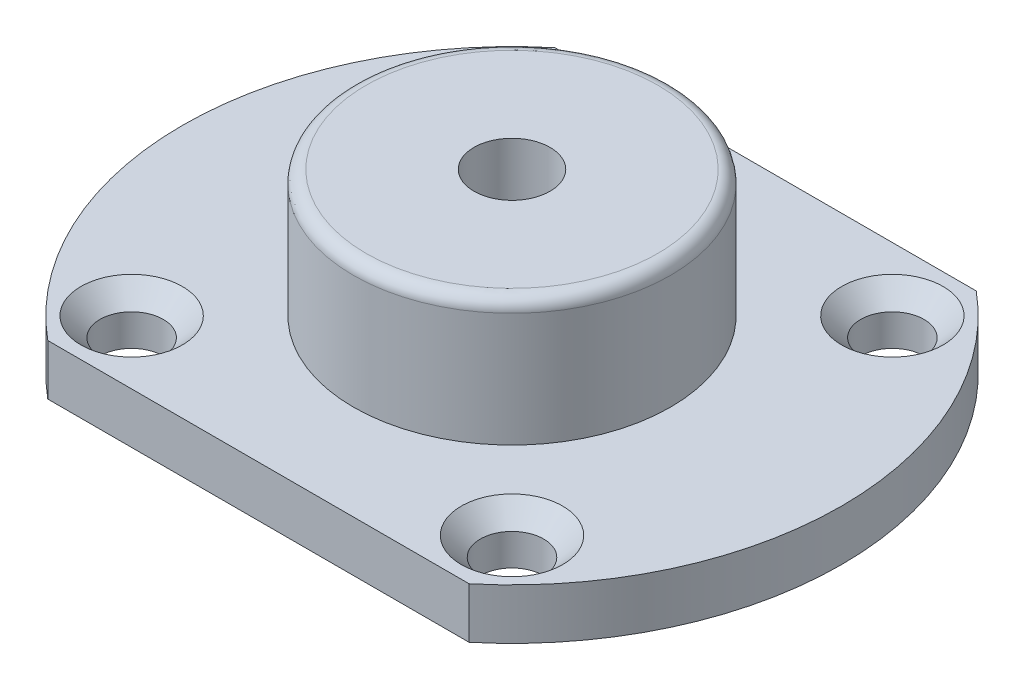
SolidWorks part; units mm, degrees
ref_plane "Спереди" through (0, 0, 0) normal (0, 0, 1) x (1, 0, 0)
ref_plane "Сверху" through (0, 0, 0) normal (0, 1, 0) x (1, 0, 0)
ref_plane "Справа" through (0, 0, 0) normal (1, 0, 0) x (0, 0, -1)
sketch "Эскиз1" plane through (0, 0, 0) normal (0, 1, 0) x (1, 0, 0)
  circle A0 centre (0, 0) radius 26
  dimension "D1" = 52
extrude "Бобышка-Вытянуть1" add sketch "Эскиз1" along normal blind 4
sketch "Эскиз2" plane through (0, 4, 0) normal (0, 1, 0) x (1, 0, 0)
  line L1 (-32.8601, -20) -> (32.8601, -20)
  line L2 (-32.8601, -20) -> (-32.8601, 20)
  line L3 (-32.8601, 20) -> (32.8601, 20)
  line L4 (32.8601, -20) -> (32.8601, 20)
  line L5 (0, 20) -> (0, -20) construction
  line L6 (-32.8601, 0) -> (32.8601, 0) construction
  point P0 (0, 0)
  dimension "D1" = 40
extrude "Вырез-Вытянуть1" cut sketch "Эскиз2" against normal blind 4 flip side to cut
sketch "Эскиз3" plane through (0, 4, 0) normal (0, 1, 0) x (1, 0, 0)
  circle A0 centre (0, 0) radius 12.5
  dimension "D1" = 25
extrude "Бобышка-Вытянуть2" add sketch "Эскиз3" along normal blind 10
fillet "Скругление1" radius 1 1 edges at (0, 14, 12.5)
sketch "Эскиз4" plane through (0, 14, 0) normal (0, 1, 0) x (1, 0, 0)
  circle A0 centre (0, 0) radius 3
  dimension "D1" = 6
extrude "Вырез-Вытянуть2" cut sketch "Эскиз4" against normal up to next
sketch "Эскиз5" plane through (0, 4, 0) normal (0, 1, 0) x (1, 0, 0)
  line L0 (0, 6.8569) -> (0, 0) construction
  line L1 (0, 0) -> (5.9462, 0) construction
  circle A0 centre (-15, 15) radius 2.5
  circle A1 centre (15, 15) radius 2.5
  circle A2 centre (15, -15) radius 2.5
  circle A3 centre (-15, -15) radius 2.5
  dimension "D1" = 5
  dimension "D2" = 30
  dimension "D3" = 30
extrude "Вырез-Вытянуть3" cut sketch "Эскиз5" against normal up to next
chamfer "Фаска1" distance 1.5 angle 45 4 edges at (15, 4, -12.5) (15, 4, 17.5) (-15, 4, 17.5) (-15, 4, -12.5)
